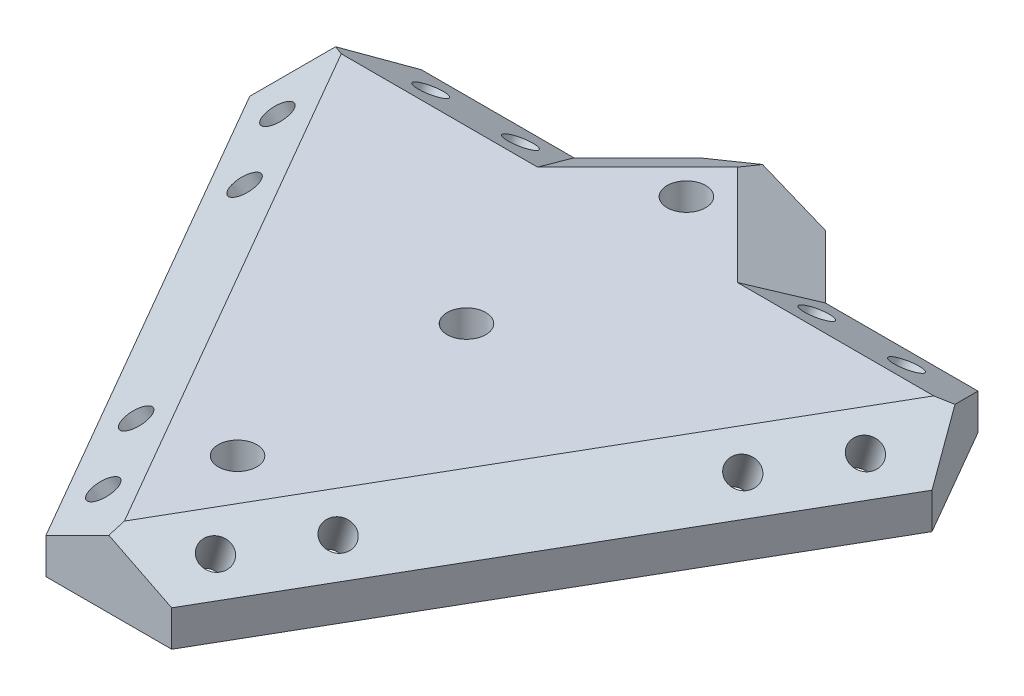
SolidWorks part; units mm, degrees
ref_plane "Front Plane" through (0, 0, 0) normal (0, 0, 1) x (1, 0, 0)
ref_plane "Top Plane" through (0, 0, 0) normal (0, 1, 0) x (1, 0, 0)
ref_plane "Right Plane" through (0, 0, 0) normal (1, 0, 0) x (0, 0, -1)
sketch "Sketch1" plane through (0, 0, 0) normal (0, 1, 0) x (1, 0, 0)
  line L0 (-31, 25.9808) -> (-14, 25.9808)
  line L1 (31, 25.9808) -> (38, 13.8564)
  line L2 (38, 13.8564) -> (7, -39.8372)
  line L3 (7, -39.8372) -> (-7, -39.8372)
  line L4 (-7, -39.8372) -> (-38, 13.8564)
  line L5 (-38, 13.8564) -> (-31, 25.9808)
  line L6 (0, 24.5) -> (0, 0) construction
  line L7 (0, 0) -> (0, -25.5) construction
  line L8 (-14, 25.9808) -> (-7, 32.9808)
  line L9 (-7, 32.9808) -> (7, 32.9808)
  line L10 (7, 32.9808) -> (14, 25.9808)
  line L11 (-7, 32.9808) -> (-7, 25.9808) construction
  line L12 (-14, 25.9808) -> (14, 25.9808) construction
  line L13 (14, 25.9808) -> (31, 25.9808)
  circle A0 centre (0, 0) radius 25.9808 construction
  circle A1 centre (0, 24.5) radius 2.15
  circle A2 centre (0, -25.5) radius 2.15
  circle A3 centre (0, 0) radius 2.15
  dimension "D4" = 50
  dimension "D6" = 4.3
  dimension "D1" = 120
  dimension "D2" = 7
  dimension "D3" = 14
  dimension "D5" = 25.5
  dimension "D7" = 62
extrude "Boss-Extrude1" add sketch "Sketch1" along normal blind 8
chamfer "Chamfer1" distance 4 angle 60 6 edges at (10.5, 8, -29.4808) (22.5, 8, -25.9808) (-10.5, 8, -29.4808) (-22.5, 8, -25.9808) (22.5, 8, 12.9904) (-22.5, 8, 12.9904) first distance on face at (10.5, 4, -29.4808) first distance on face at (22.5, 4, -25.9808) first distance on face at (-10.5, 4, -29.4808) first distance on face at (-22.5, 4, -25.9808) first distance on face at (22.5, 4, 12.9904) first distance on face at (-22.5, 4, 12.9904)
sketch "Sketch2" plane through (7.125, 14.25, 4.1136) normal (0.433, 0.866, 0.25) x (0.9014, -0.416, -0.1201)
  line L0 (28.4284, 12.8968) -> (-0.9707, -31.2019) construction
  line L1 (34.2527, 14.4222) -> (-0.1387, -37.1649) construction
  line L2 (28.4284, 12.8968) -> (34.2527, 14.4222) construction
  line L3 (-0.9707, -31.2019) -> (-0.1387, -37.1649) construction
  line L4 (28.4284, 12.8968) -> (31.7566, 10.678) construction
  line L5 (28.4284, 12.8968) -> (25.1002, 15.1156) construction
  line L6 (-7.9045, -34.3914) -> (28.7057, 20.5239) construction
  circle A0 centre (28.4284, 12.8968) radius 1.6
  circle A1 centre (-0.9707, -31.2019) radius 1.6
  circle A2 centre (4.5763, -22.8814) radius 1.6
  circle A3 centre (22.8814, 4.5763) radius 1.6
  circle A4 centre (28.4284, 12.8968) radius 5 construction
  dimension "D1" = 3.2
  dimension "D3" = 10
  dimension "D4" = 10
  dimension "D5" = 33
  dimension "D6" = 10
  dimension "D2" = 53
extrude "Cut-Extrude1" cut sketch "Sketch2" against normal up to next
sketch "Sketch3" plane through (7.125, 14.25, 4.1136) normal (0.433, 0.866, 0.25) x (0.9014, -0.416, -0.1201)
  circle A0 centre (28.4284, 12.8968) radius 3
  circle A1 centre (-0.9707, -31.2019) radius 3
  circle A2 centre (22.8814, 4.5763) radius 3
  circle A3 centre (4.5763, -22.8814) radius 3
  dimension "D1" = 6
extrude "Cut-Extrude2" cut sketch "Sketch3" against normal up to next from offset 6 offset against normal yes
pattern_circular "CirPattern1" count 3 every 120 about axis through (0, 8, 0) along (0, 1, 0) of "Cut-Extrude1", "Cut-Extrude2"
equation "\"D4@Sketch2\"=\"D3@Sketch2\""
